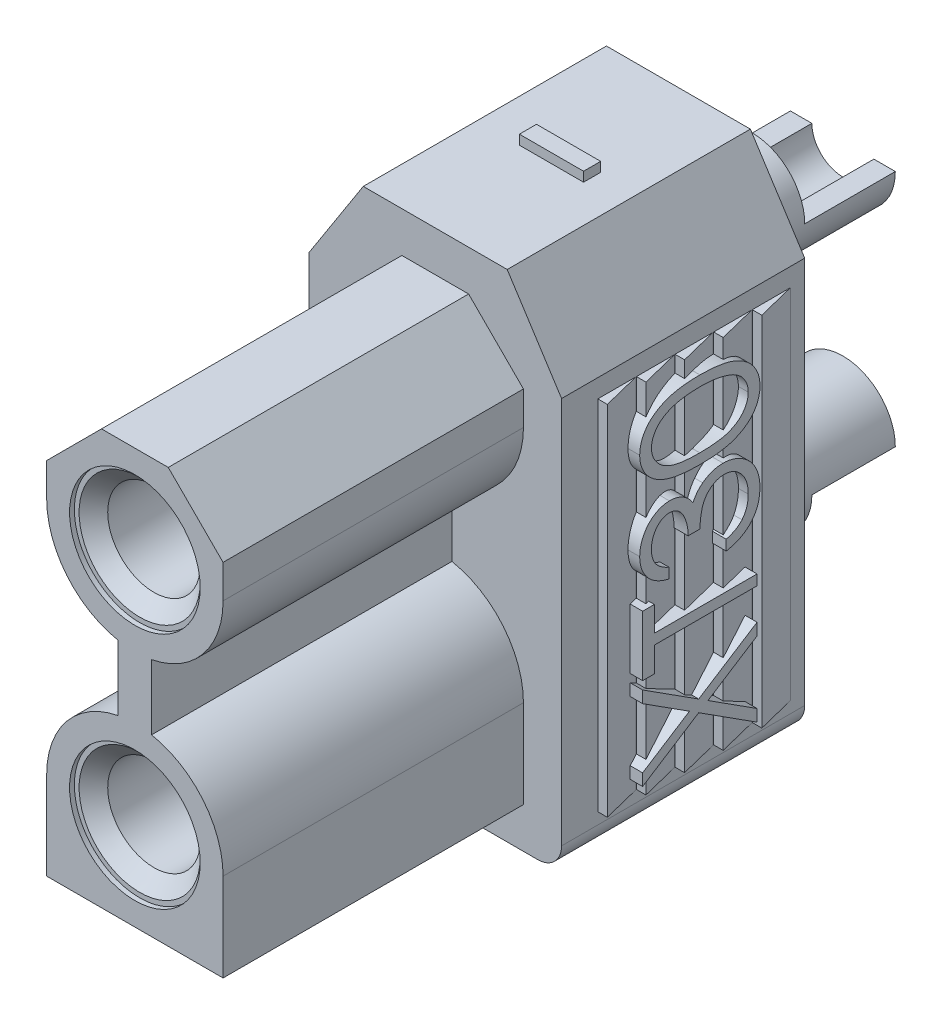
SolidWorks part; units mm, degrees
ref_plane "Front Plane" through (0, 0, 0) normal (0, 0, 1) x (1, 0, 0)
ref_plane "Top Plane" through (0, 0, 0) normal (0, 1, 0) x (1, 0, 0)
ref_plane "Right Plane" through (0, 0, 0) normal (1, 0, 0) x (0, 0, -1)
sketch "Sketch3" plane through (0, 0, 0) normal (0, 0, 1) x (1, 0, 0)
  line L0 (0, 1.0104) -> (0, 9.9104) construction
  line L1 (0, 5.4604) -> (-1.9, 5.4604) construction
  line L2 (0, 5.4604) -> (1.9, 5.4604) construction
  line L3 (0, 9.9104) -> (-1.1, 9.9104) construction
  line L4 (-1.1, 9.9104) -> (-1.1, 8.5104) construction
  line L5 (1.9, 1.0104) -> (-1.9, 1.0104)
  line L6 (-1.9, 1.0104) -> (-1.9, 8.6659)
  line L7 (-1.9, 8.6659) -> (-1.1, 9.9104)
  line L8 (-1.1, 9.9104) -> (1.1, 9.9104)
  line L9 (1.9, 1.0104) -> (1.9, 8.6659)
  line L10 (1.9, 8.6659) -> (1.1, 9.9104)
  line L11 (2.15, 0.2604) -> (-2.15, 0.2604)
  line L12 (-2.65, 0.7604) -> (-2.65, 8.8862)
  line L13 (-2.65, 8.8862) -> (-1.5095, 10.6604)
  line L14 (-1.5095, 10.6604) -> (1.5095, 10.6604)
  line L15 (2.65, 8.8862) -> (1.5095, 10.6604)
  line L16 (2.65, 0.7604) -> (2.65, 8.8862)
  line L17 (2.65, 0.2604) -> (-2.65, 0.2604) construction
  line L18 (2.65, 0.2604) -> (2.65, 8.8862) construction
  line L19 (-2.65, 0.2604) -> (-2.65, 8.8862) construction
  arc A0 (2.15, 0.2604) -> (2.65, 0.7604) centre (2.15, 0.7604) ccw
  arc A1 (-2.15, 0.2604) -> (-2.65, 0.7604) centre (-2.15, 0.7604) cw
  point P22 (2.65, 0.2604)
  dimension "D9" = 0.5
  dimension "D1" = 8.9
  dimension "D2" = 1.9
  dimension "D3" = 1.9
  dimension "D4" = 1.1
  dimension "D5" = 1.4
  dimension "D8" = 10.4
  dimension "D6" = 0.75
extrude "Boss-Extrude2" add sketch "Sketch3" along normal blind 5.1
sketch "Sketch4" plane through (0, 0, 0) normal (0, 0, 1) x (1, 0, 0)
  line L6 (-1.5, 10.0104) -> (1.4, 10.0104)
  line L7 (-2, 9.5104) -> (-2, 1.0104)
  line L8 (-2, 1.0104) -> (1.9, 1.0104)
  line L9 (1.9, 9.5104) -> (1.9, 1.0104)
  arc A0 (1.4, 10.0104) -> (1.9, 9.5104) centre (1.4, 9.5104) cw
  arc A1 (-1.5, 10.0104) -> (-2, 9.5104) centre (-1.5, 9.5104) ccw
  dimension "D1" = 0.5
extrude "Boss-Extrude3" add sketch "Sketch4" along normal up to surface (5.1 mm away) from offset 1.45 up to face at (0, 5.1159, 5.1)
sketch "Sketch6" plane through (0, 0, 0) normal (0, 1, 0) x (1, 0, 0)
  line L0 (2.65, -0.3) -> (2.65, -1.1)
  line L1 (2.65, -5.1) -> (2.65, 0) construction
  line L2 (2.65, -1.1) -> (2.85, -1.1)
  line L3 (2.65, 0) -> (1.5095, 0) construction
  line L4 (0, 0) -> (0, -2.7855) construction
  line L5 (2.85, -1.1) -> (2.65, -0.3)
  line L6 (2.65, -1.11) -> (2.65, -1.91)
  line L7 (2.65, -1.91) -> (2.85, -1.91)
  line L8 (2.85, -1.91) -> (2.65, -1.11)
  line L9 (2.65, -1.92) -> (2.65, -2.72)
  line L10 (2.65, -2.72) -> (2.85, -2.72)
  line L11 (2.85, -2.72) -> (2.65, -1.92)
  line L12 (2.65, -2.73) -> (2.65, -3.53)
  line L13 (2.65, -3.53) -> (2.85, -3.53)
  line L14 (2.85, -3.53) -> (2.65, -2.73)
  line L15 (2.65, -3.54) -> (2.65, -4.34)
  line L16 (2.65, -4.34) -> (2.85, -4.34)
  line L17 (2.85, -4.34) -> (2.65, -3.54)
  line L18 (-2.85, -4.34) -> (-2.65, -3.54)
  line L19 (-2.65, -4.34) -> (-2.85, -4.34)
  line L20 (-2.65, -3.54) -> (-2.65, -4.34)
  line L21 (-2.85, -3.53) -> (-2.65, -2.73)
  line L22 (-2.65, -3.53) -> (-2.85, -3.53)
  line L23 (-2.65, -2.73) -> (-2.65, -3.53)
  line L24 (-2.85, -2.72) -> (-2.65, -1.92)
  line L25 (-2.65, -2.72) -> (-2.85, -2.72)
  line L26 (-2.65, -1.92) -> (-2.65, -2.72)
  line L27 (-2.85, -1.91) -> (-2.65, -1.11)
  line L28 (-2.65, -1.91) -> (-2.85, -1.91)
  line L29 (-2.65, -1.11) -> (-2.65, -1.91)
  line L30 (-2.85, -1.1) -> (-2.65, -0.3)
  line L31 (-2.65, -1.1) -> (-2.85, -1.1)
  line L32 (-2.65, -0.3) -> (-2.65, -1.1)
  dimension "D1" = 0.3
  dimension "D2" = 0.8
  dimension "D3" = 5
  dimension "D4" = 0.2
extrude "Boss-Extrude4" add sketch "Sketch6" along normal blind 7.5 from offset 1
sketch "Sketch7" plane through (0, 0, 0) normal (0, 0, 1) x (1, 0, 0)
  line L0 (-1.9, 1.0104) -> (1.9, 1.0104) construction
  line L1 (0, 2.9604) -> (0, 7.9604) construction
  line L2 (1.1, 9.9104) -> (-1.1, 9.9104) construction
  circle A0 centre (0, 2.9604) radius 1.1
  circle A1 centre (0, 7.9604) radius 1.1
  dimension "D1" = 2.2
  dimension "D2" = 2.2
  dimension "D3" = 5
  dimension "D4" = 1.95
  dimension "D5" = 1.95
extrude "Boss-Extrude5" add sketch "Sketch7" along normal up to surface (5.1 mm away) and the other way blind 3.45 separate body up to face at (0, 5.1159, 5.1)
sketch "Sketch8" plane through (0, 0, -3.45) normal (0, 0, -1) x (-1, 0, 0)
  circle A1 centre (0, 2.9604) radius 0.65
  circle A2 centre (0, 7.9604) radius 0.65
extrude "Cut-Extrude1" cut sketch "Sketch8" against normal blind 3
sketch "Sketch9" plane through (0, 0, 0) normal (1, 0, 0) x (0, 0, -1)
  line L0 (3.45, 6.8604) -> (3.45, 9.0604) construction
  line L1 (3.45, 7.9604) -> (1.55, 7.9604)
  line L2 (3.45, 7.9604) -> (3.45, 9.0604)
  line L3 (3.45, 9.0604) -> (1.55, 9.0604)
  line L4 (1.55, 7.9604) -> (1.55, 9.0604)
  line L5 (3.45, 9.0604) -> (-5.1, 9.0604) construction
  line L6 (3.45, 1.8604) -> (3.45, 4.0604) construction
  line L7 (3.45, 2.9604) -> (1.7, 2.9604)
  line L8 (3.45, 2.9604) -> (3.45, 1.8604)
  line L9 (3.45, 1.8604) -> (1.7, 1.8604)
  line L10 (1.7, 2.9604) -> (1.7, 1.8604)
  line L11 (-5.1, 1.8604) -> (3.45, 1.8604) construction
  dimension "D1" = 1.9
extrude "Cut-Extrude2" cut sketch "Sketch9" against normal through all and the other way through all
chamfer "Chamfer1" distance 0.65 angle 45 1 edges at (-0.65, 7.9604, -0.45)
chamfer "Chamfer3" distance 0.65 angle 45 1 edges at (-0.65, 2.9604, -0.45)
sketch "Sketch10" plane through (0, 0, 5.1) normal (0, 0, 1) x (1, 0, 0)
  circle A0 centre (0, 7.9604) radius 0.97
  circle A1 centre (0, 2.9604) radius 0.97
  circle A3 centre (0, 7.9604) radius 1.37
  circle A4 centre (0, 2.9604) radius 1.37
  point P6 (0, 0)
  point P7 (0, 0)
  point P8 (0, 0)
  dimension "D1" = 0.4
extrude "Boss-Extrude6" add sketch "Sketch10" along normal blind 6.2 separate body
sketch "Sketch12" plane through (0, 0.2604, 0) normal (0, -1, 0) x (1, 0, 0)
  line L0 (0, 0) -> (0, 1) construction
  line L1 (0, 1) -> (-1.45, 1) construction
  line L2 (-1.45, 1) -> (0.8, 1) construction
  text T0 "+\r\n"
  dimension "D1" = 1
  dimension "D2" = 1.45
extrude "Boss-Extrude7" add sketch "Sketch12" along normal blind 0.2
sketch "Sketch13" plane through (0, 10.6604, 0) normal (0, 1, 0) x (-1, 0, 0)
  line L0 (0.2478, 0.1887) -> (0.2478, 1.1887) construction
  line L1 (0.2478, 1.1887) -> (-1.1522, 1.1887) construction
  line L2 (-1.1522, 1.1887) -> (1.0478, 1.1887) construction
  text T0 "-\r\n"
  dimension "D1" = 1
  dimension "D2" = 1.4
extrude "Boss-Extrude8" add sketch "Sketch13" along normal blind 0.2
sketch "Sketch14" plane through (-2.65, 0, 0) normal (-1, 0, 0) x (0, 0, 1)
  line L0 (0.3, 4.75) -> (1.3, 4.75) construction
  line L1 (0.3, 8.5) -> (0.3, 1) construction
  line L2 (1.3, 4.75) -> (1.3, 8.35) construction
  line L3 (1.3, 8.35) -> (1.3, 1.15) construction
  text T0 "XT30\r\n" font "Century Gothic" height 2.4
  dimension "D1" = 1
  dimension "D2" = 3.6
  dimension "D3" = 7.2
extrude "Boss-Extrude9" add sketch "Sketch14" along normal blind 0.3
sketch "Sketch15" plane through (2.65, 0, 0) normal (1, 0, 0) x (0, 0, -1)
  line L0 (-0.3, 4.75) -> (-1.3, 4.75) construction
  line L2 (-1.3, 4.75) -> (-1.3, 1.15) construction
  line L3 (-1.3, 1.15) -> (-1.3, 8.35) construction
  text T0 "XT30\r\n" font "Century Gothic" height 2.4
  dimension "D1" = 1
  dimension "D2" = 3.6
  dimension "D3" = 7.2
extrude "Boss-Extrude10" add sketch "Sketch15" along normal blind 0.3
chamfer "Chamfer4" distance 0.3 angle 45 1 edges at (0.97, 2.9604, 11.3)
chamfer "Chamfer5" distance 0.3 angle 45 1 edges at (0.97, 7.9604, 11.3)
sketch "Sketch17" plane through (0, 0, 5.1) normal (0, 0, 1) x (1, 0, 0)
  line L0 (0, 2.9604) -> (-1.85, 2.9604) construction
  line L1 (0, 1.1104) -> (0, 9.8104) construction
  line L2 (0, 1.1104) -> (-1.85, 1.1104)
  line L3 (-1.85, 1.1104) -> (-1.85, 2.9604)
  line L4 (0, 2.9604) -> (1.85, 2.9604) construction
  line L5 (0, 1.1104) -> (1.85, 1.1104)
  line L6 (1.85, 1.1104) -> (1.85, 2.9604)
  line L7 (0.7, 9.8104) -> (-0.7, 9.8104)
  line L8 (0, 7.9604) -> (-1.85, 7.9604) construction
  line L9 (-0.7, 9.8104) -> (-2.8213, 7.689) construction
  line L10 (-1.85, 7.9604) -> (-1.85, 8.6604)
  line L11 (-1.85, 8.6604) -> (-0.7, 9.8104)
  line L12 (1.85, 7.9604) -> (1.85, 8.6604)
  line L13 (1.85, 8.6604) -> (0.7, 9.8104)
  circle A0 centre (0, 2.9604) radius 1.37 construction
  circle A1 centre (0, 7.9604) radius 1.37 construction
  arc A2 (-1.85, 2.9604) -> (1.85, 2.9604) centre (0, 2.9604) cw
  arc A3 (-1.85, 7.9604) -> (1.85, 7.9604) centre (0, 7.9604) ccw
  circle A7 centre (0, 7.9604) radius 1.37
  circle A8 centre (0, 2.9604) radius 1.37
  dimension "D1" = 1.85
  dimension "D2" = 8.7
  dimension "D3" = 1.85
  dimension "D4" = 1.85
  dimension "D5" = 1.85
extrude "Boss-Extrude11" add sketch "Sketch17" along normal blind 6.3 separate body
sketch "Sketch18" plane through (0, 0, 5.1) normal (0, 0, 1) x (1, 0, 0)
  line L0 (0, 6.1104) -> (0, 4.8104) construction
  line L2 (-0.35, 6.3204) -> (0.35, 6.3204)
  line L3 (-0.35, 6.3204) -> (-0.35, 4.6003)
  line L4 (-0.35, 4.6003) -> (0.35, 4.6003)
  line L5 (0.35, 6.3204) -> (0.35, 4.6003)
  line L6 (-0.35, 6.3204) -> (0.35, 4.6003) construction
  line L7 (-0.35, 4.6003) -> (0.35, 6.3204) construction
  arc A0 (-1.85, 7.9604) -> (1.85, 7.9604) centre (0, 7.9604) ccw construction
  arc A1 (1.85, 2.9604) -> (-1.85, 2.9604) centre (0, 2.9604) ccw construction
  point P8 (0, 5.4604)
  point P13 (0, 0)
  dimension "D1" = 0.7
extrude "Boss-Extrude12" add sketch "Sketch18" along normal up to surface (6.3 mm away) up to face at (0, 2.4979, 11.4)
